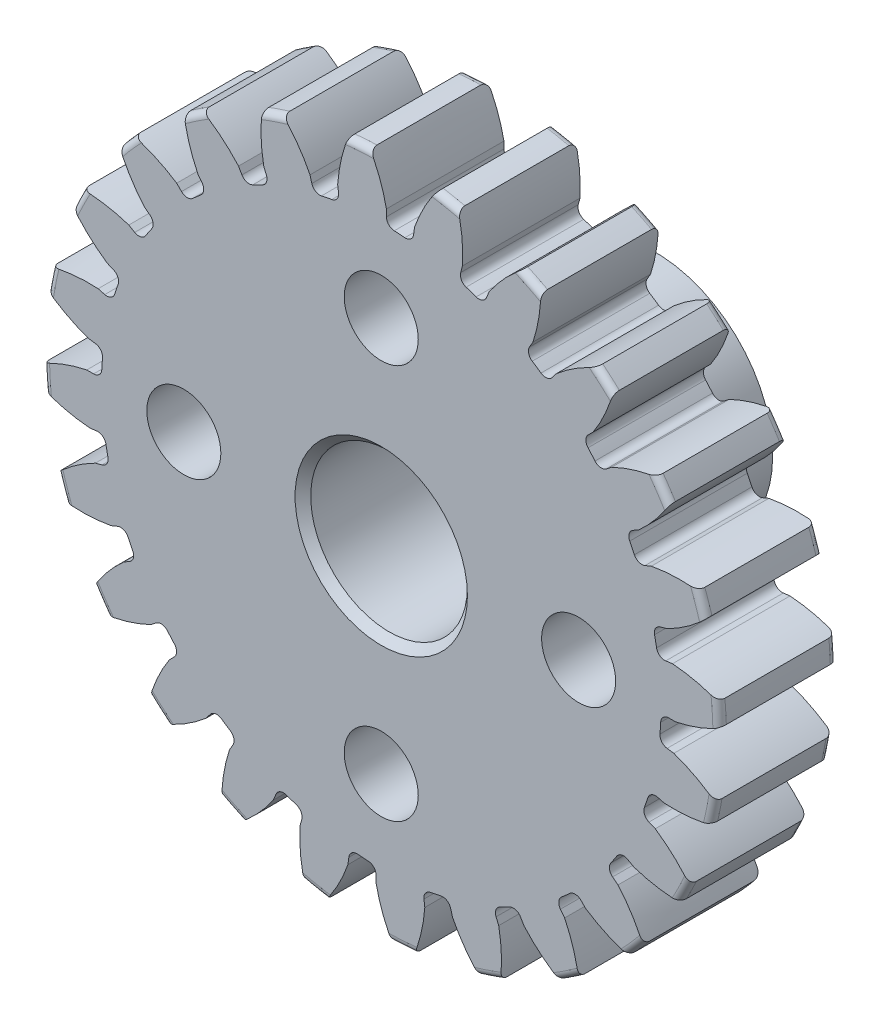
SolidWorks part; units mm, degrees
material "Plain Carbon Steel"
ref_plane "Front" through (0, 0, 0) normal (0, 0, 1) x (1, 0, 0)
ref_plane "Top" through (0, 0, 0) normal (0, 1, 0) x (1, 0, 0)
ref_plane "Right" through (0, 0, 0) normal (1, 0, 0) x (0, 0, -1)
sketch "Sketch1" plane through (0, 0, 0) normal (0, 0, 1) x (1, 0, 0)
  line L0 (-304.8, 0) -> (304.8, 0) construction
  circle A0 centre (0, 0) radius 13.716
  circle A1 centre (0, 0) radius 12.7 construction
  circle A3 centre (0, 0) radius 11.3348 construction
  dimension "D1" = 2.3812
extrude "Boss-Extrude1" add sketch "Sketch1" against normal blind 4.7625
sketch "Sketch2" plane through (0, 0, 0) normal (1, 0, 0) x (0, 0, -1)
  line L0 (4.7625, 0) -> (11.0998, 0)
  line L1 (4.7625, 0) -> (4.7625, 6.35)
  line L2 (4.7625, 6.35) -> (11.0998, 6.35)
  line L3 (11.0998, 6.35) -> (11.0998, 0)
  point P5 (11.0998, -6.35)
  point P6 (0, -13.716)
  point P7 (4.7625, -13.716)
  point P9 (0, 13.716)
revolve "Revolve1" add sketch "Sketch2" angle 360 mid plane about L0
fillet "Fillet2" radius 0.2743 3 edges at (13.716, 0, -4.7625) (13.716, 0, 0) (6.35, 0, -4.7625)
sketch "Sketch3" plane through (0, 0, 0) normal (0, 0, 1) x (1, 0, 0)
  line L0 (0, 0) -> (0, 13.716) construction
  line L1 (-4.0817, 11.2144) -> (0, 12.7)
  line L2 (-9.5921, 12.7) -> (9.5921, 12.7) construction
  line L3 (-9.0136, 9.4193) -> (9.0136, 15.9807) construction
  line L4 (-4.0817, 11.2144) -> (0, 0) construction
  line L5 (-9.8295, 6.7678) -> (0, 0) construction
  line L6 (-9.8295, 6.7678) -> (-3.193, 16.4066) construction
  line L7 (-2.8353, 11.5924) -> (0, 0) construction
  line L8 (-2.8353, 11.5924) -> (0.1182, 12.3148) construction
  arc A0 (-4.0817, 11.2144) -> (-9.8295, 6.7678) centre (0, 0) ccw
  circle A1 centre (0, 0) radius 12.7 construction
  circle A2 centre (0, 0) radius 11.9341 construction
  arc A3 (-4.0817, 11.2144) -> (-2.8353, 11.5924) centre (0, 0) cw
  circle A4 centre (0, 0) radius 13.716 construction
  point P6 (0, 12.7)
  dimension "D1" = 4.3437
  dimension "D3" = 11.7025
  dimension "D5" = 3.0406
  dimension "D2" = 7.3842
  dimension "D4" = 1.3031
sketch "Sketch4" plane through (0, 0, 0) normal (0, 0, 1) x (1, 0, 0)
  line L0 (0, 0) -> (0.8288, 12.6457) construction
  line L1 (0.2102, 11.9322) -> (0.2102, 11.3328)
  line L2 (0, 12.7) -> (1.6577, 12.5913) construction
  line L3 (1.3491, 11.8576) -> (1.2708, 11.2633)
  line L4 (0.2102, 11.3328) -> (0, 0) construction
  line L5 (0, 0) -> (0, 13.716) construction
  line L6 (-9.8295, 6.7678) -> (-3.193, 16.4066) construction
  line L7 (-9.8295, 6.7678) -> (-3.193, 16.4066) construction
  arc A0 (1.2708, 11.2633) -> (0.2102, 11.3328) centre (0, 0) ccw
  arc A1 (0, 12.7) -> (1.6577, 12.5913) centre (0, 0) cw construction
  circle A2 centre (0, 0) radius 12.7 construction
  circle A3 centre (0, 0) radius 11.9341 construction
  circle A4 centre (0, 0) radius 11.3348 construction
  arc A5 (5.3072, 15.8494) -> (-3.193, 16.4066) centre (0, 0) ccw
  spline S0 degree 2 poles (-3.193, 16.4066) (-0.3735, 14.7207) (0.2102, 11.9322) knots 0 0 0 1 1 1
  spline S1 degree 2 poles (5.3072, 15.8494) (2.2918, 14.5461) (1.3491, 11.8576) knots 0 0 0 1 1 1
  dimension "D1" = 1.6624
extrude "Cut-Extrude1" cut sketch "Sketch4" against normal through all
fillet "Fillet1" radius 0.3325 2 edges at (1.2708, 11.2633, -2.3813) (0.2102, 11.3328, -2.3813)
pattern_circular "CirPattern1" count 24 over 360 about axis through (0, 0, -4.7625) along (0, 0, 1) of "Cut-Extrude1", "Fillet1"
sketch "Sketch5" plane through (0, 0, 0) normal (0, 0, 1) x (1, 0, 0)
  line L0 (0, 4.3663) -> (0, 0) construction
  line L1 (-1.1906, 2.9433) -> (1.1906, 2.9433) construction
  line L2 (-1.1906, 2.9433) -> (-1.1906, 4.3663) construction
  line L3 (-1.1906, 4.3663) -> (1.1906, 4.3663) construction
  line L4 (1.1906, 2.9433) -> (1.1906, 4.3663) construction
  line L5 (-1.1906, 2.9433) -> (1.1906, 4.3663) construction
  line L6 (-1.1906, 4.3663) -> (1.1906, 2.9433) construction
  circle A0 centre (0, 0) radius 3.175
  point P3 (0, 3.6548)
  point P8 (0, 3.175)
  point P9 (0, -3.175)
  dimension "Bore Min" = 6.35
  dimension "Keyway Wd" = 2.3813
  dimension "Keyway Dpt." = 1.1913
extrude "Cut-Extrude2" cut sketch "Sketch5" against normal through all
chamfer "Chamfer1" distance 0.3175 angle 45 3 edges at (6.35, 0, -11.0998) (3.175, 0, 0) (3.175, 0, -11.0998)
sketch "Pitch Dia" plane through (0, 0, 0) normal (0, 0, 1) x (1, 0, 0)
  circle A0 centre (0, 0) radius 12.7 construction
  circle A1 centre (0, 0) radius 12.7 construction
sketch "Sketch19" plane through (0, 0, -4.7625) normal (0, 0, -1) x (-1, 0, 0)
  circle A0 centre (0, 0) radius 4.7625
  dimension "D1" = 9.525
extrude "Cut-Extrude9" cut sketch "Sketch19" along normal through all flip side to cut
sketch "Sketch20" plane through (0, 0, -4.7625) normal (0, 0, -1) x (-1, 0, 0)
  line L0 (0, 15.0033) -> (0, -15.1457) construction
  line L1 (-18.4026, 0) -> (14.9499, 0) construction
  circle A0 centre (0, 7.9997) radius 1.5
  circle A1 centre (7.9997, 0) radius 1.5
  circle A2 centre (0, -7.9997) radius 1.5
  circle A3 centre (-7.9997, 0) radius 1.5
  dimension "D1" = 3
  dimension "D2" = 3
  dimension "D3" = 3
  dimension "D4" = 3
  dimension "D5" = 15.9995
  dimension "D6" = 15.9995
extrude "Cut-Extrude8" cut sketch "Sketch20" against normal through all contours A3 | A0 | A1 | A2 region at (0, 7.9997, -4.7625) region at (-7.9997, 0, -4.7625) region at (0, -7.9997, -4.7625) region at (7.9997, 0, -4.7625)
chamfer "Chamfer4" distance 1.5 angle 45 4 edges at (-1.5, -7.9997, -4.7625) (-9.4997, 0, -4.7625) (-1.5, 7.9997, -4.7625) (6.4997, 0, -4.7625)
sketch "Sketch21" plane through (0, 0, 0) normal (0, 1, 0) x (1, 0, 0)
  line L0 (0, 10.7823) -> (0, 0.3175) construction
  line L2 (-0.3071, 4.7625) -> (-1.4495, 4.7625) construction
  circle A0 centre (0, 6.985) radius 0.9525
  point P6 (0, 6.0325)
  dimension "D1" = 1.905
  dimension "D2" = 1.27
extrude "Cut-Extrude10" cut sketch "Sketch21" against normal through all both and the other way through all
equation "\"D1@Boss-Extrude1\" = \"Face Wd@Sketch2\""
equation "\"D2@Sketch3\"= \"D1@Sketch3\" * 1.7"
equation "\"D3@Sketch3\"= \"D1@Sketch3\" + \"D2@Sketch3\" - .001"
equation "\"D4@Sketch3\" = \"D1@Sketch3\"*.3"
equation "\"D5@Sketch3\" = \"D1@Sketch3\"-\"D4@Sketch3\""
equation "\"D1@Sketch4\" = 1.5708/(\"Number of Teeth@Sketch1\"/\"Ptich Dia@Sketch1\")"
equation "\"D1@Chamfer1\" = \"B Hub Dia@Sketch2\"*.025"
equation "\"D1@CirPattern1\" = \"Number of Teeth@Sketch1\""
equation "\"D1@Fillet1\" = \"D1@Sketch4\"*.2"
equation "\"D1@Fillet2\" = \"OD@Sketch1\"*.01"
equation "\"D1@Sketch1\" = 2.250/(\"Number of Teeth@Sketch1\"/\"Ptich Dia@Sketch1\")"
